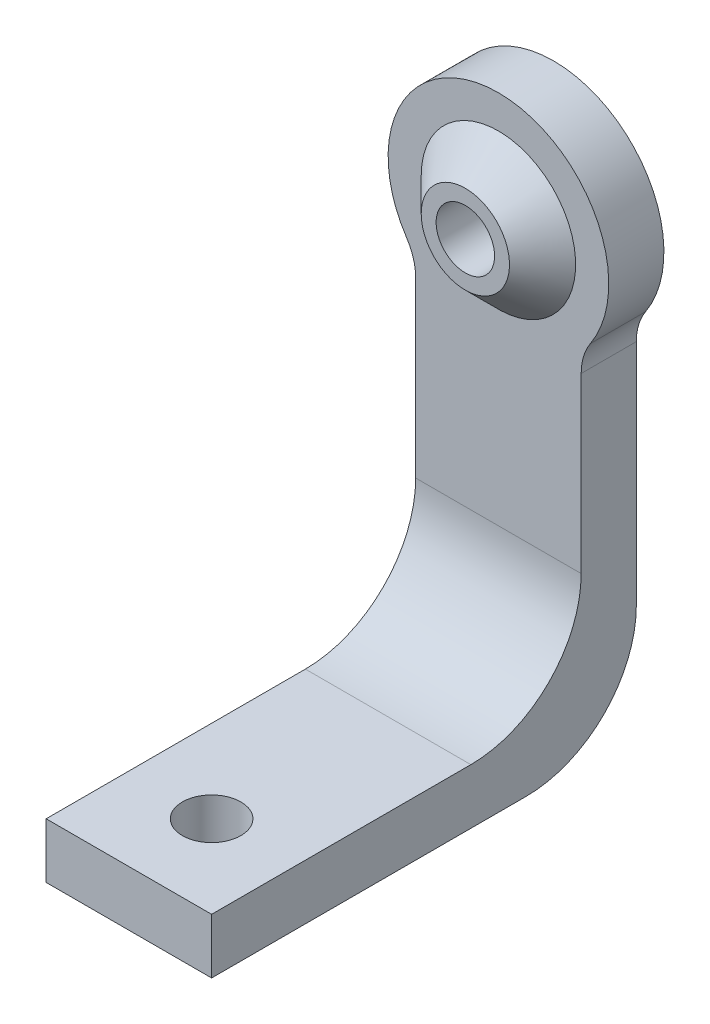
SolidWorks part; units mm, degrees
ref_plane "Front Plane" through (0, 0, 0) normal (0, 0, 1) x (1, 0, 0)
ref_plane "Top Plane" through (0, 0, 0) normal (0, 1, 0) x (1, 0, 0)
ref_plane "Right Plane" through (0, 0, 0) normal (1, 0, 0) x (0, 0, -1)
sketch "Sketch8" plane through (0, 0, 0) normal (-1, 0, 0) x (0, 0, 1)
  line L1 (-16.75, 2.5) -> (16.75, 2.5)
  line L2 (-16.75, 2.5) -> (-16.75, -2.5)
  line L3 (-16.75, -2.5) -> (16.75, -2.5)
  line L4 (16.75, 2.5) -> (16.75, -2.5)
  line L5 (-16.75, 2.5) -> (16.75, -2.5) construction
  line L6 (-16.75, -2.5) -> (16.75, 2.5) construction
  line L8 (-21.75, -2.5) -> (-16.75, -2.5)
  line L9 (-21.75, -2.5) -> (-21.75, 41.5)
  line L10 (-21.75, 41.5) -> (-16.75, 41.5)
  line L11 (-16.75, -2.5) -> (-16.75, 41.5)
  line L12 (-21.75, -2.5) -> (-16.75, 41.5) construction
  line L13 (-21.75, 41.5) -> (-16.75, -2.5) construction
  point P0 (0, 0)
  point P9 (-19.25, 19.5)
  dimension "D1" = 5
  dimension "D2" = 33.5
  dimension "D3" = 0
  dimension "D4" = 5
  dimension "D5" = 0
  dimension "D6" = 44
  dimension "D7" = 0
extrude "Boss-Extrude5" add sketch "Sketch8" along normal blind 7.5 and the other way blind 7.5 contours L2 L3 L1 | L2 L11 L10 L9 L8 | L2 L1 L4 L3 region at (0, 0, 0) region at (0, 19.5, -19.25)
sketch "Sketch9" plane through (0, 0, -16.75) normal (0, 0, 1) x (1, 0, 0)
  line L1 (-7.5, -2.5) -> (-7.5, 41.5) construction
  line L2 (7.5, 41.5) -> (-7.5, 41.5) construction
  circle A0 centre (0, 36.5) radius 10
  dimension "D1" = 20
  dimension "D2" = 7.5
  dimension "D3" = 5
extrude "Boss-Extrude6" add sketch "Sketch9" against normal blind 5
sketch "Sketch11" plane through (0, 0, -21.75) normal (0, 0, -1) x (-1, 0, 0)
  circle A0 centre (0, 36.5) radius 2.65
  arc A1 (7.5, 29.8856) -> (-7.5, 29.8856) centre (0, 36.5) ccw construction
  dimension "D1" = 5.3
  dimension "D2" = 0
extrude "Cut-Extrude7" cut sketch "Sketch11" against normal blind 5
sketch "Sketch12" plane through (0, 0, -16.75) normal (0, 0, 1) x (1, 0, 0)
  circle A0 centre (0, 36.5) radius 4
  circle A1 centre (0, 36.5) radius 2.65 construction
  circle A2 centre (0, 36.5) radius 2.65
  dimension "D2" = 0
  dimension "D3" = 8
  dimension "D4" = 0
  dimension "D1" = 0
extrude "Boss-Extrude7" add sketch "Sketch12" along normal blind 3
chamfer "Chamfer1" distance 3 angle 45 1 edges at (4, 36.5, -16.75)
fillet "Fillet1" radius 10 2 edges at (0, -2.5, -21.75) (0, 2.5, -16.75)
fillet "Fillet2" radius 5 2 edges at (7.5, 29.8856, -19.25) (-7.5, 29.8856, -19.25)
sketch "Sketch13" plane through (0, 2.5, 0) normal (0, 1, 0) x (1, 0, 0)
  line L0 (7.5, -16.75) -> (-7.5, -16.75) construction
  line L1 (7.5, 6.75) -> (7.5, -16.75) construction
  circle A0 centre (0, -9.25) radius 2.65
  dimension "D2" = 5.3
  dimension "D1" = 7.5
  dimension "D3" = 7.5
extrude "Cut-Extrude8" cut sketch "Sketch13" against normal blind 50
sketch "Sketch14" plane through (0, -2.5, 0) normal (0, -1, 0) x (1, 0, 0)
  circle A0 centre (0, 9.25) radius 4
  circle A1 centre (0, 9.25) radius 2.65
  dimension "D1" = 8
extrude "Boss-Extrude8" add sketch "Sketch14" along normal blind 3
chamfer "Chamfer2" distance 3 angle 45 1 edges at (0, -2.5, 5.25)
